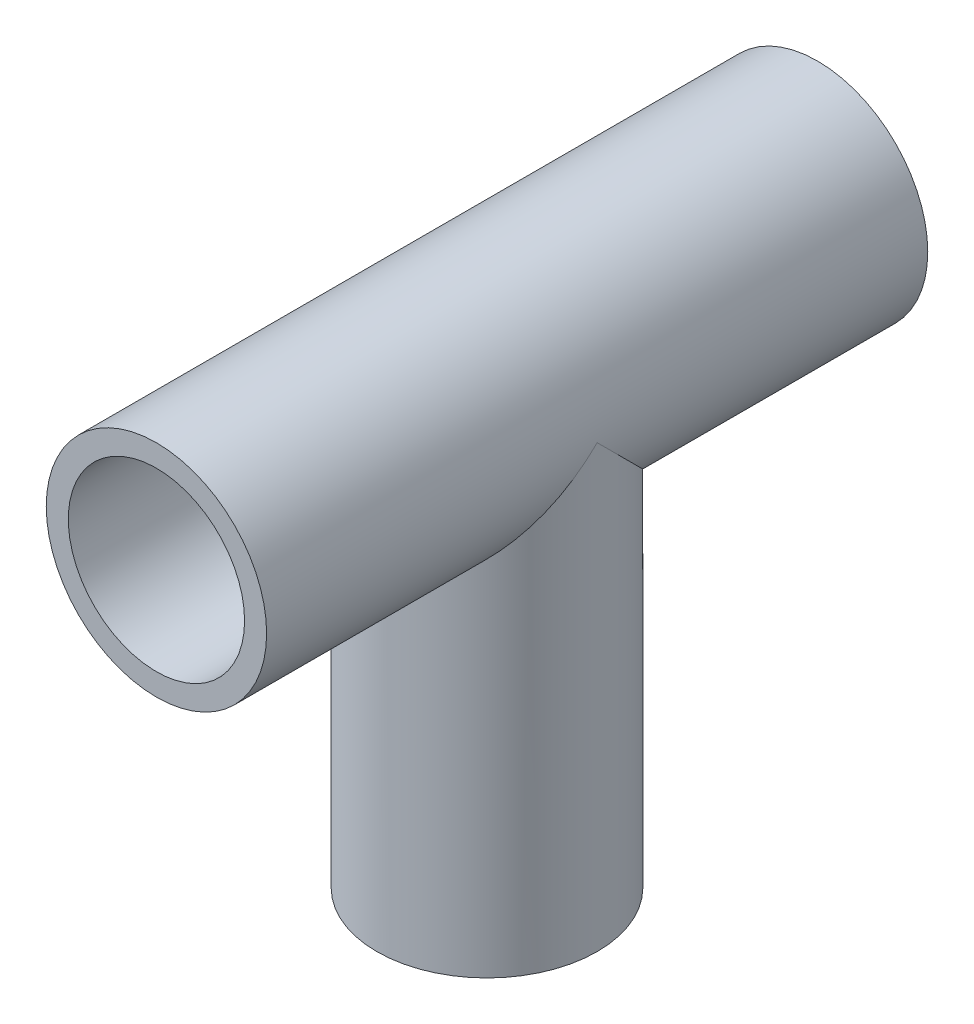
SolidWorks part; units mm, degrees
ref_plane "前视基准面" through (0, 0, 0) normal (0, 0, 1) x (1, 0, 0)
ref_plane "上视基准面" through (0, 0, 0) normal (0, 1, 0) x (1, 0, 0)
ref_plane "右视基准面" through (0, 0, 0) normal (1, 0, 0) x (0, 0, -1)
sketch "草图2" plane through (0, 0, 0) normal (0, 1, 0) x (1, 0, 0)
  circle A0 centre (0, 0) radius 2.5
  circle A1 centre (0, 0) radius 2
  dimension "D1" = 5
  dimension "D2" = 0.5
extrude "凸台-拉伸1" add sketch "草图2" along normal blind 10
sketch "草图3" plane through (0, 0, 0) normal (0, 0, 1) x (1, 0, 0)
  line L0 (2, 10) -> (-2, 10) construction
  circle A0 centre (0, 10) radius 2.5
  circle A1 centre (0, 10) radius 2
  dimension "D1" = 0.5
extrude "凸台-拉伸2" add sketch "草图3" along normal blind 7.5 and the other way blind 7.5
sketch "草图4" plane through (0, 0, 7.5) normal (0, 0, 1) x (1, 0, 0)
  circle A0 centre (0, 10) radius 2 construction
  circle A1 centre (0, 10) radius 2
extrude "切除-拉伸1" cut sketch "草图4" against normal through all
sketch "草图5" plane through (0, 0, 0) normal (0, -1, 0) x (1, 0, 0)
  circle A0 centre (0, 0) radius 2 construction
  circle A1 centre (0, 0) radius 2
extrude "切除-拉伸3" cut sketch "草图5" against normal up to surface (8 mm away) up to face at (2, 10, -7.5)
